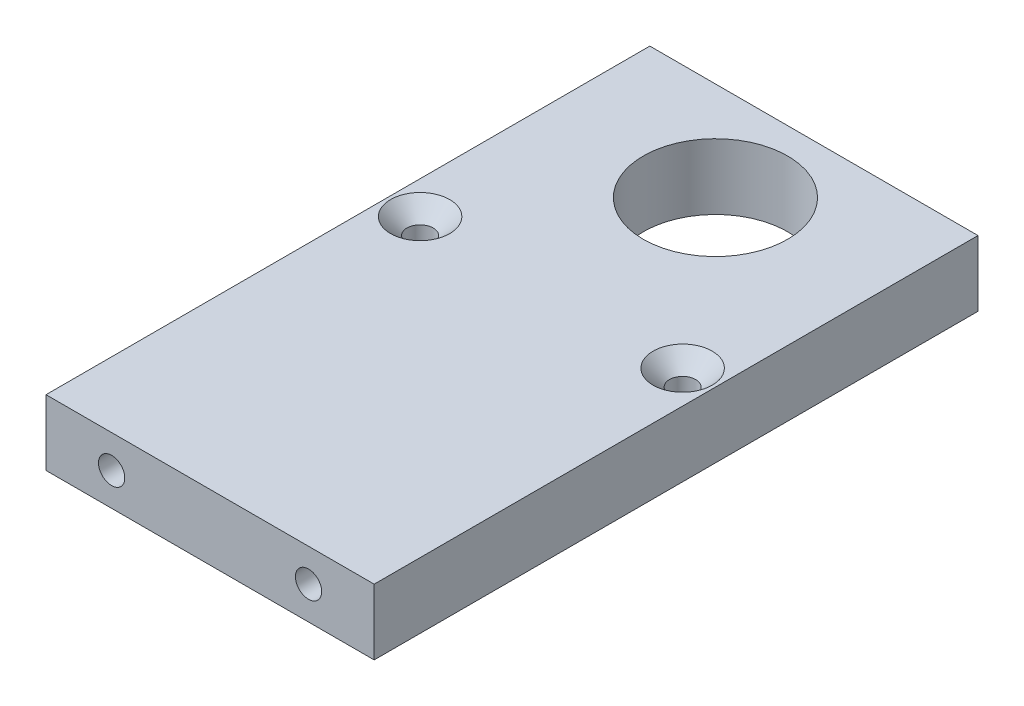
SolidWorks part; units mm, degrees
material "PVC rigide"
ref_plane "Plan de face" through (0, 0, 0) normal (0, 0, 1) x (1, 0, 0)
ref_plane "Plan de dessus" through (0, 0, 0) normal (0, 1, 0) x (1, 0, 0)
ref_plane "Plan de droite" through (0, 0, 0) normal (1, 0, 0) x (0, 0, -1)
sketch "Esquisse1" plane through (0, 0, 0) normal (0, 1, 0) x (1, 0, 0)
  line L0 (-6.4914, -72.1179) -> (-6.4914, 19.8821) construction
  line L1 (-31.4914, 19.8821) -> (18.5086, 19.8821)
  line L2 (-31.4914, 19.8821) -> (-31.4914, -72.1179)
  line L3 (-31.4914, -72.1179) -> (18.5086, -72.1179)
  line L4 (18.5086, 19.8821) -> (18.5086, -72.1179)
  line L6 (-41.3411, -20.1179) -> (33.4874, -20.1179) construction
  circle A1 centre (-6.4914, 4.8821) radius 11
  circle A2 centre (-26.4914, -20.1179) radius 2
  circle A3 centre (13.5086, -20.1179) radius 2
  dimension "D5" = 22
  dimension "D10" = 4
  dimension "D1" = 50
  dimension "D2" = 92
  dimension "D6" = 15
  dimension "D7" = 52
  dimension "D8" = 5
  dimension "D9" = 5
extrude "Boss.-Extru.1" add sketch "Esquisse1" along normal blind 10
chamfer "Chanfrein1" distance 2.5 angle 45 2 edges at (13.5086, 10, 22.1179) (-26.4914, 10, 22.1179)
sketch "Esquisse2" plane through (0, 0, 72.1179) normal (0, 0, 1) x (1, 0, 0)
  line L0 (-31.4914, 5) -> (18.5086, 5) construction
  line L1 (-31.4914, 10) -> (-31.4914, 0) construction
  line L2 (18.5086, 10) -> (18.5086, 0) construction
  circle A0 centre (-21.4914, 5) radius 2
  circle A1 centre (8.5086, 5) radius 2
  dimension "D1" = 4
  dimension "D2" = 10
  dimension "D3" = 10
extrude "Enlèv. mat.-Extru.1" cut sketch "Esquisse2" against normal blind 10
sketch "Esquisse3" plane through (0, 0, 0) normal (0, -1, 0) x (1, 0, 0)
  line L0 (-31.4914, 57.1179) -> (18.5086, 57.1179) construction
  line L1 (-31.4914, -19.8821) -> (-31.4914, 72.1179) construction
  line L2 (18.5086, 72.1179) -> (18.5086, -19.8821) construction
  line L3 (-31.4914, 72.1179) -> (18.5086, 72.1179) construction
  circle A0 centre (-6.4914, 57.1179) radius 11
  dimension "D2" = 22
  dimension "D1" = 15
extrude "Enlèv. mat.-Extru.2" cut sketch "Esquisse3" against normal blind 7
